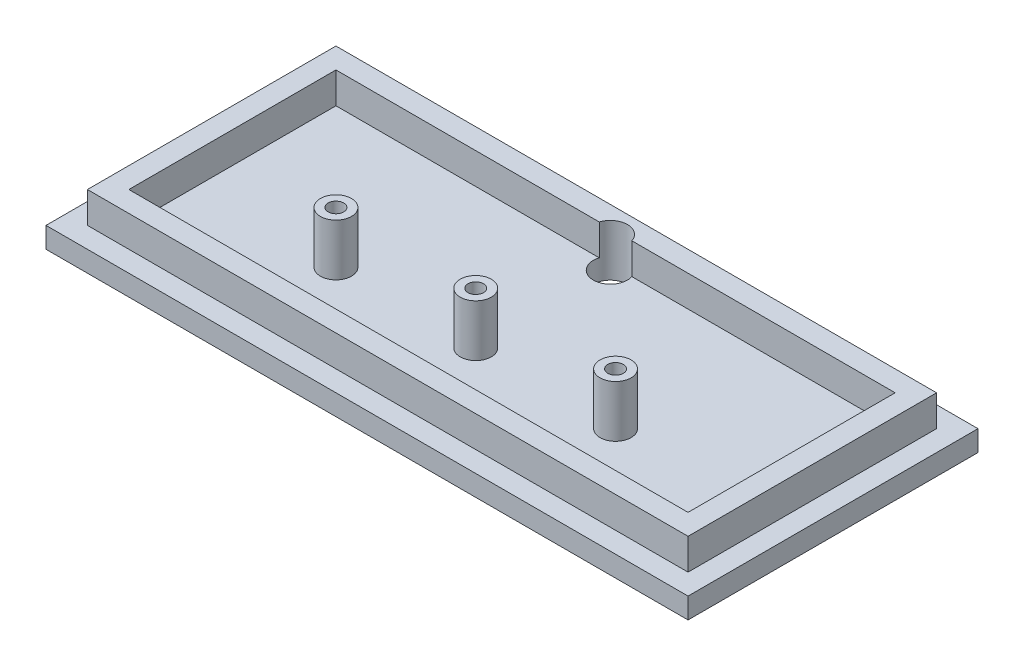
SolidWorks part; units mm, degrees
ref_plane "Front" through (0, 0, 0) normal (0, 0, 1) x (1, 0, 0)
ref_plane "Top" through (0, 0, 0) normal (0, 1, 0) x (1, 0, 0)
ref_plane "Right" through (0, 0, 0) normal (1, 0, 0) x (0, 0, -1)
sketch "Sketch1" plane through (0, 0, 0) normal (0, 1, 0) x (1, 0, 0)
  line L1 (0, 0) -> (62, 0)
  line L2 (0, 0) -> (0, 28)
  line L3 (0, 28) -> (62, 28)
  line L4 (62, 0) -> (62, 28)
  dimension "D1" = 28
  dimension "D2" = 62
extrude "Boss-Extrude1" add sketch "Sketch1" along normal blind 2
sketch "Sketch2" plane through (0, 2, 0) normal (0, 1, 0) x (1, 0, 0)
  line L0 (62, 28) -> (0, 28) construction
  line L1 (2, 26) -> (60, 26)
  line L2 (2, 26) -> (2, 2)
  line L3 (2, 2) -> (60, 2)
  line L4 (60, 26) -> (60, 2)
  line L5 (0, 28) -> (0, 0) construction
  line L6 (0, 0) -> (62, 0) construction
  line L7 (62, 0) -> (62, 28) construction
  line L9 (4, 24) -> (58, 24)
  line L10 (4, 24) -> (4, 4)
  line L11 (4, 4) -> (58, 4)
  line L12 (58, 24) -> (58, 4)
  dimension "D1" = 2
  dimension "D2" = 2
  dimension "D3" = 2
  dimension "D4" = 2
  dimension "D5" = 2
  dimension "D6" = 2
  dimension "D7" = 2
  dimension "D8" = 2
extrude "Boss-Extrude2" add sketch "Sketch2" along normal blind 3
sketch "Sketch3" plane through (0, 2, 0) normal (0, 1, 0) x (1, 0, 0)
  line L0 (4, 24) -> (4, 4) construction
  line L2 (4, 4) -> (58, 4) construction
  circle A0 centre (17.5, 10.5) radius 1.5
  circle A1 centre (31, 10.5) radius 1.5
  circle A2 centre (44.5, 10.5) radius 1.5
  circle A3 centre (17.5, 10.5) radius 0.75
  circle A4 centre (31, 10.5) radius 0.75
  circle A5 centre (44.5, 10.5) radius 0.75
  dimension "D1" = 3
  dimension "D2" = 3
  dimension "D3" = 3
  dimension "D8" = 1.5
  dimension "D9" = 1.5
  dimension "D10" = 1.5
  dimension "D4" = 13.5
  dimension "D5" = 13.5
  dimension "D6" = 13.5
  dimension "D7" = 6.5
extrude "Boss-Extrude3" add sketch "Sketch3" along normal blind 5
hole_wizard "Ø3.3 (3.3) Diameter Hole1" positions "Sketch5" profile "Sketch4" hole size "Ø3.3" standard "ANSI Metric" end condition through all
sketch "Sketch5" plane through (0, 0, 0) normal (0, -1, 0) x (-1, 0, 0)
  line L0 (-62, 28) -> (0, 28) construction
  line L1 (0, 28) -> (0, 0) construction
  point P0 (-31, 23.5)
  dimension "D1" = 4.5
  dimension "D2" = 31
sketch "Sketch4" plane through (31, 0, -23.5) normal (1, 0, 0) x (0, 0, -1)
  line L0 (0, 0) -> (0, 7)
  line L1 (0, 7) -> (1.65, 7)
  line L2 (1.65, 7) -> (1.65, 0)
  line L5 (1.65, 0) -> (0, 0)
  line L11 (0, -6.35) -> (0, 107.95) construction
  dimension "Thru Hole Dia." = 3.3
  dimension "Thru Hole Depth" = 7
